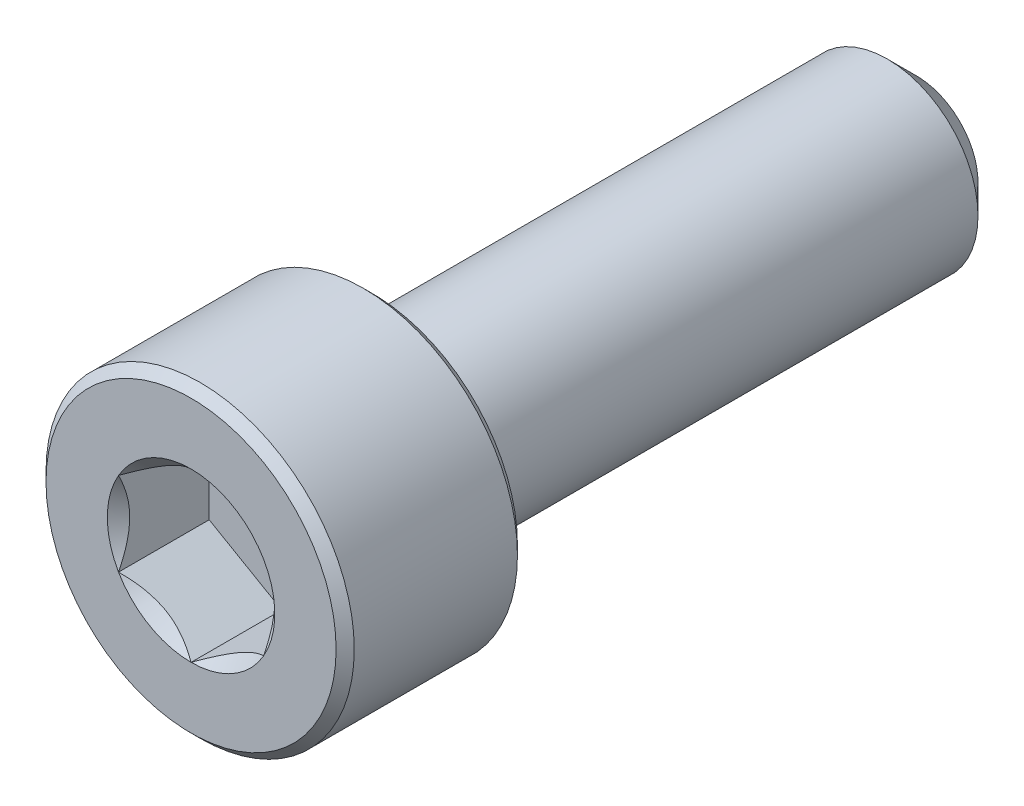
SolidWorks part; units mm, degrees
ref_plane "Front Plane" through (0, 0, 0) normal (0, 0, 1) x (1, 0, 0)
ref_plane "Top Plane" through (0, 0, 0) normal (0, 1, 0) x (1, 0, 0)
ref_plane "Right Plane" through (0, 0, 0) normal (1, 0, 0) x (0, 0, -1)
sketch "Sketch1" plane through (0, 0, 0) normal (1, 0, 0) x (0, 0, -1)
  line L0 (-10, 0) -> (10, 0) construction
  line L1 (10, 0) -> (10, 1.7) construction
  line L2 (10, 1.7) -> (9.2, 2.5) construction
  line L3 (9.2, 2.5) -> (-5, 2.5) construction
  line L5 (-5, 2.5) -> (-5, 4.25) construction
  line L6 (-5, 4.25) -> (-10, 4.25) construction
  line L7 (-10, 4.25) -> (-10, 0) construction
  line L8 (10, 1.7) -> (10, 2.5) construction
  line L9 (9.95, 2.5866) -> (10.35, 1.8938) construction
  line L10 (10.35, 1.8938) -> (10.75, 2.5866) construction
  line L11 (10.75, 2.5866) -> (9.95, 2.5866) construction
  line L12 (10.35, 2.5866) -> (10.35, 2.5) construction
  line L13 (10.35, 1.8938) -> (10.35, 1.9804) construction
  line L14 (10.3, 1.9804) -> (10.4, 1.9804) construction
  line L15 (10, 2.5) -> (10.7, 2.5) construction
  line L16 (9.975, 2.5433) -> (10.725, 2.5433) construction
  line L17 (10, 0) -> (10, -2.5) construction
  line L18 (-5.25, 4.25) -> (-5, 4) construction
  line L19 (-9.75, 4.25) -> (-10, 4) construction
  point P0 (-10, 2)
  point P3 (7.2, 2.5)
  point P4 (0, 0)
  point P22 (10.35, 1.9804)
  point P24 (-5, 2.5)
  point P25 (10.35, 2.5)
  point P28 (10.35, 2.5433)
  point P29 (7.2, -2.5)
  point P31 (-7.5, 4.25)
  point P37 (-5.875, 4.25)
  point P38 (-9.625, 4.25)
  point P41 (-7.5, 0)
  dimension "head height" = 5
  dimension "D1" = 45
  dimension "Head Diameter" = 8.5
  dimension "Thread Size" = 5
  dimension "drive size" = 4
  dimension "Thread Pitch" = 0.8
  dimension "D2" = 0.1
  dimension "D3" = 0.8
  dimension "D4" = 2.8
  dimension "D7" = 0.25
  dimension "D8" = 0.25
  dimension "D9" = 0.25
  dimension "D10" = 0.125
  dimension "D11" = 0.625
  dimension "length" = 15
  dimension "Drive Depth" = 2.5
sketch "Sketch2" plane through (0, 0, 0) normal (1, 0, 0) x (0, 0, -1)
  line L1 (-9.75, 4.25) -> (-5.25, 4.25)
  line L4 (9.2, 2.5) -> (10, 1.7)
  line L5 (10, 1.7) -> (10, 0)
  line L6 (-5.25, 4.25) -> (-5, 4) construction
  line L7 (10, 0) -> (-10, 0)
  line L8 (-9.75, 4.25) -> (-10, 4) construction
  line L9 (-5.25, 4.25) -> (-5, 4)
  line L10 (-9.75, 4.25) -> (-10, 4)
  line L11 (-10, 4) -> (-10, 0)
  line L12 (-5, 4) -> (-5, 2.5)
  line L13 (-5, 2.5) -> (9.2, 2.5)
revolve "Revolve1" add sketch "Sketch2" angle 360 about L7
sketch "Sketch3" plane through (0, 0, 10) normal (0, 0, 1) x (1, 0, 0)
  line L1 (0, 2.3094) -> (-2, 1.1547)
  line L2 (-2, 1.1547) -> (-2, -1.1547)
  line L3 (-2, -1.1547) -> (0, -2.3094)
  line L4 (0, -2.3094) -> (2, -1.1547)
  line L5 (2, -1.1547) -> (2, 1.1547)
  line L6 (2, 1.1547) -> (0, 2.3094)
  circle A0 centre (0, 0) radius 2 construction
  dimension "D1" = 4
extrude "Cut-Extrude1" cut sketch "Sketch3" against normal up to vertex (2.5 mm away) up to point (0, 0, 7.5)
sketch "Sketch4" plane through (0, 0, 10) normal (0, 0, 1) x (1, 0, 0)
  circle A0 centre (0, 0) radius 2.3094
extrude "Cut-Extrude2" cut sketch "Sketch4" against normal blind 0.5 draft 45
ref_plane "Plane1" [suppressed] through (0, 0, 5) normal (0, 0, 1) x (1, 0, 0)
split "Split1" [suppressed] bodies to split 106
sketch "Sketch6" [suppressed] plane through (0, 0, -10) normal (0, 0, -1) x (-1, 0, 0)
  circle A0 centre (0, 0) radius 2.5
curve "Helix/Spiral1" [suppressed] pitch 0.8 height 15.8 turns 19.75
sketch "Sketch7" [suppressed] plane through (0, 0, 0) normal (1, 0, 0) x (0, 0, -1)
  line L0 (9.975, 2.5433) -> (10.725, 2.5433)
  line L1 (10.725, 2.5433) -> (10.4, 1.9804)
  line L2 (10.4, 1.9804) -> (10.3, 1.9804)
  line L3 (10.3, 1.9804) -> (9.975, 2.5433)
sweep "Cut-Sweep1" [suppressed] cut profiles "Sketch7" path "Helix/Spiral1"
sketch "Sketch8" [suppressed] plane through (0, 0, 5) normal (0, 0, -1) x (-1, 0, 0)
  circle A0 centre (0, 0) radius 2.5
extrude "Boss-Extrude1" [suppressed] add sketch "Sketch8" along normal through all draft 45
ref_plane "Plane2" [suppressed] through (0, 0, 7.5) normal (0, 0, 1) x (1, 0, 0)
sketch "Sketch9" [suppressed] plane through (0, 0, 7.5) normal (0, 0, 1) x (1, 0, 0)
  line L0 (0, 4.1331) -> (0.1113, 4.2485)
  line L1 (0, 4.1331) -> (-0.1113, 4.2485)
  line L2 (0, 4.25) -> (0, 0) construction
  line L3 (-0.1113, 4.2485) -> (0, 0) construction
  line L4 (0, 0) -> (0.1113, 4.2485) construction
  arc A0 (0.1113, 4.2485) -> (-0.1113, 4.2485) centre (0, 0) ccw
  circle A1 centre (0, 0) radius 4.1331 construction
  dimension "D1" = 8.5
  dimension "D2" = 8.2662
  dimension "D3" = 3
extrude "Cut-Extrude4" [suppressed] cut sketch "Sketch9" against normal up to vertex and the other way up to vertex
pattern_circular "CirPattern2" [suppressed] count 96 over 360 about axis through (0, 0, 10) along (0, 0, -1) of bodies 113
equation "\"D2@Sketch1\" = \"Thread Pitch@Sketch1\" / 8"
equation "\"D3@Sketch1\" = \"Thread Pitch@Sketch1\""
equation "\"D3@Helix/Spiral1\" = \"length@Sketch1\" + \"Thread Pitch@Sketch1\""
equation "\"D4@Helix/Spiral1\" = \"Thread Pitch@Sketch1\""
equation "\"D4@Sketch1\" = \"Thread Pitch@Sketch1\" * 3.5"
equation "\"D7@Sketch1\"=\"head height@Sketch1\"*.05"
equation "\"D8@Sketch1\"=\"D7@Sketch1\""
equation "\"D9@Sketch1\"=\"D7@Sketch1\""
equation "\"D10@Sketch1\"=\"D7@Sketch1\"/2"
equation "\"D11@Sketch1\"=\"D10@Sketch1\"*5"
equation "\"D1@CirPattern2\"=( 360 / \"D3@Sketch9\" )*0.8"
equation "\"D1@Sketch3\" = \"drive size@Sketch1\""
equation "\"D2@Sketch9\"=\"Head Diameter@Sketch1\" * 0.9725"
